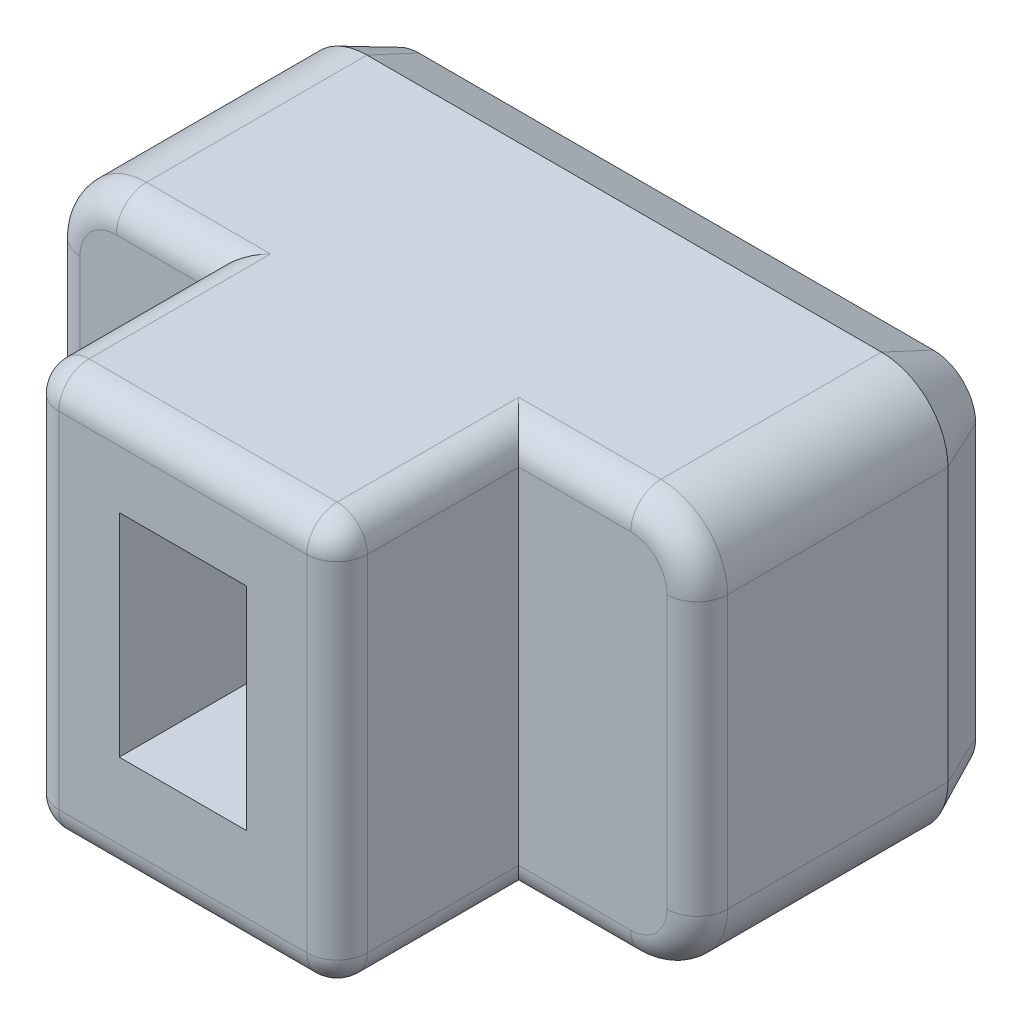
SolidWorks part; units mm, degrees
ref_plane "Plan de face" through (0, 0, 0) normal (0, 0, 1) x (1, 0, 0)
ref_plane "Plan de dessus" through (0, 0, 0) normal (0, 1, 0) x (1, 0, 0)
ref_plane "Plan de droite" through (0, 0, 0) normal (1, 0, 0) x (0, 0, -1)
sketch "Esquisse2" plane through (0, 0, 0) normal (0, 0, 1) x (1, 0, 0)
  line L1 (1.1, 0) -> (9.6, 0)
  line L2 (0, 1.1) -> (0, 5.6)
  line L3 (1.1, 6.7) -> (9.6, 6.7)
  line L4 (10.7, 1.1) -> (10.7, 5.6)
  arc A0 (9.6, 6.7) -> (10.7, 5.6) centre (9.6, 5.6) cw
  arc A1 (9.6, 0) -> (10.7, 1.1) centre (9.6, 1.1) ccw
  arc A2 (1.1, 0) -> (0, 1.1) centre (1.1, 1.1) cw
  arc A3 (0, 5.6) -> (1.1, 6.7) centre (1.1, 5.6) cw
  point P7 (10.7, 6.7)
  point P12 (0, 0)
  point P15 (0, 6.7)
  dimension "D3" = 1.1
  dimension "D1" = 10.7
  dimension "D2" = 6.7
extrude "Boss.-Extru.1" add sketch "Esquisse2" along normal blind 8
sketch "Esquisse3" plane through (0, 0, 8) normal (0, 0, 1) x (1, 0, 0)
  line L0 (0, 5.6) -> (0, 1.1) construction
  line L1 (4.15, 5.25) -> (6.25, 5.25)
  line L2 (4.15, 5.25) -> (4.15, 1.75)
  line L3 (4.15, 1.75) -> (6.25, 1.75)
  line L4 (6.25, 5.25) -> (6.25, 1.75)
  line L5 (10.7, 1.1) -> (10.7, 5.6) construction
  line L6 (9.6, 6.7) -> (1.1, 6.7) construction
  line L7 (1.1, 0) -> (9.6, 0) construction
  dimension "D1" = 2.1
  dimension "D2" = 3.5
  dimension "D3" = 4.15
  dimension "D4" = 4.45
  dimension "D5" = 1.45
  dimension "D6" = 1.75
extrude "Enlèv. mat.-Extru.1" cut sketch "Esquisse3" against normal blind 3
sketch "Esquisse4" plane through (0, 0, 8) normal (0, 0, 1) x (1, 0, 0)
  line L0 (2.65, 6.7) -> (2.65, 0)
  line L1 (9.6, 6.7) -> (1.1, 6.7) construction
  line L2 (1.1, 0) -> (9.6, 0) construction
  line L3 (2.65, 0) -> (7.75, 0)
  line L4 (7.75, 0) -> (7.75, 6.7)
  line L5 (7.75, 6.7) -> (2.65, 6.7)
  line L6 (4.15, 5.25) -> (4.15, 1.75) construction
  line L7 (6.25, 1.75) -> (6.25, 5.25) construction
  dimension "D1" = 1.5
  dimension "D2" = 1.5
extrude "Enlèv. mat.-Extru.2" cut sketch "Esquisse4" against normal blind 3 flip side to cut
fillet "Congé1" radius 0.5 18 edges at (8.675, 0, 5) (10.3778, 0.3222, 5) (10.7, 3.35, 5) (10.3778, 6.3778, 5) (1.875, 6.7, 5) (0.3222, 6.3778, 5) (1.875, 0, 5) (0.3222, 0.3222, 5) (7.75, 6.7, 6.5) (2.65, 6.7, 6.5) (7.75, 0, 6.5) (2.65, 0, 6.5) (2.65, 3.35, 8) (5.2, 6.7, 8) (7.75, 3.35, 8) (5.2, 0, 8) (8.675, 6.7, 5) (0, 3.35, 5)
chamfer "Chanfrein1" distance 0.4 angle 65 8 edges at (5.35, 0, 0) (10.3778, 0.3222, 0) (0.3222, 0.3222, 0) (10.7, 3.35, 0) (0, 3.35, 0) (10.3778, 6.3778, 0) (0.3222, 6.3778, 0) (5.35, 6.7, 0) first distance on face at (5.35, 3.35, 0)
ref_plane "Plan1" through (0, 0, 0.2) normal (0, 0, 1) x (1, 0, 0)
sketch "Esquisse5" plane through (0, 0, 0.2) normal (0, 0, 1) x (1, 0, 0)
  line L0 (-0.9378, 5.3566) -> (11.6517, 5.3566) construction
  text T0 "NAV" font "Century Gothic" height 4
extrude "Enlèv. mat.-Extru.3" cut sketch "Esquisse5" against normal blind 0.3
extrude "Boss.-Extru.2" add sketch "Esquisse5<3>" against normal blind 0.2 from offset 0.2 offset against normal yes
sketch "Esquisse5<3>" plane through (0, 0, 0.2) normal (0, 0, 1) x (1, 0, 0) same geometry as "Esquisse5"
